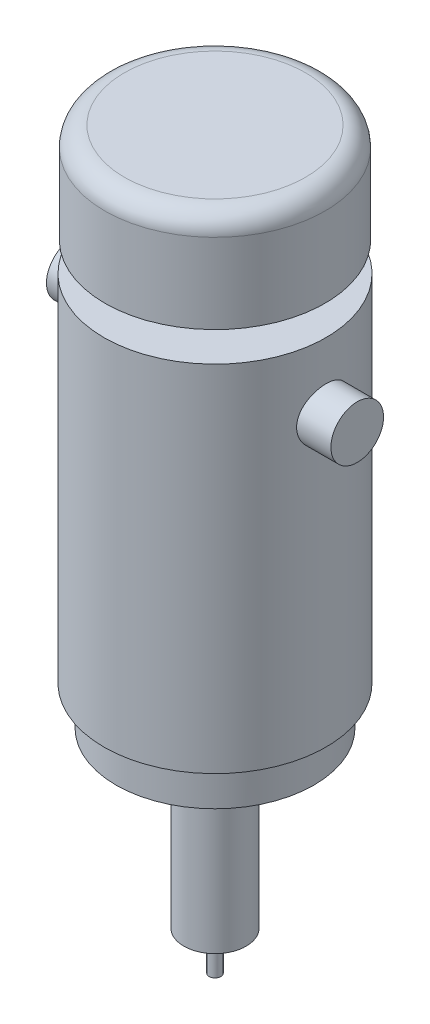
SolidWorks part; units mm, degrees
ref_plane "Front Plane" through (0, 0, 0) normal (0, 0, 1) x (1, 0, 0)
ref_plane "Top Plane" through (0, 0, 0) normal (0, 1, 0) x (1, 0, 0)
ref_plane "Right Plane" through (0, 0, 0) normal (1, 0, 0) x (0, 0, -1)
sketch "Sketch1" plane through (0, 0, 0) normal (0, 1, 0) x (1, 0, 0)
  circle A0 centre (0, 0) radius 28.5
  dimension "D1" = 57
extrude "Boss-Extrude1" add sketch "Sketch1" along normal mid plane 91
sketch "Sketch4" plane through (0, -45.5, 0) normal (0, -1, 0) x (1, 0, 0)
  circle A0 centre (0, 0) radius 25.4
  dimension "D1" = 50.8
extrude "Boss-Extrude4" add sketch "Sketch4" along normal blind 10
sketch "Sketch5" plane through (0, -55.5, 0) normal (0, -1, 0) x (1, 0, 0)
  circle A0 centre (0, 0) radius 12.65
  dimension "D1" = 25.3
extrude "Boss-Extrude5" add sketch "Sketch5" along normal blind 2.5
sketch "Sketch2" plane through (0, -58, 0) normal (0, -1, 0) x (1, 0, 0)
  circle A0 centre (0, 0) radius 8
  dimension "D1" = 16
extrude "Boss-Extrude2" add sketch "Sketch2" along normal blind 42
sketch "Sketch6" plane through (0, 45.5, 0) normal (0, 1, 0) x (1, 0, 0)
  circle A0 centre (0, 0) radius 4
  dimension "D1" = 8
extrude "Boss-Extrude6" add sketch "Sketch6" along normal blind 33
sketch "Sketch7" plane through (0, 78.5, 0) normal (0, 1, 0) x (1, 0, 0)
  circle A0 centre (0, 0) radius 28.25
  dimension "D1" = 56.5
extrude "Boss-Extrude7" add sketch "Sketch7" against normal blind 25.5
fillet "Fillet1" radius 5 1 edges at (0, 78.5, 28.25)
sketch "Sketch3" plane through (0, -100, 0) normal (0, -1, 0) x (1, 0, 0)
  circle A0 centre (0, 0) radius 1.5
  dimension "D1" = 3
extrude "Boss-Extrude3" add sketch "Sketch3" along normal blind 10
sketch "Sketch8" plane through (0, 0, 0) normal (1, 0, 0) x (0, 0, -1)
  line L0 (28.5, 45.5) -> (-28.5, 45.5) construction
  line L1 (0, 0) -> (0, 73.5) construction
  line L2 (-28.25, 73.5) -> (28.25, 73.5) construction
  circle A0 centre (0, 28.5) radius 6.75
  dimension "D1" = 13.5
  dimension "D2" = 17
extrude "Boss-Extrude8" add sketch "Sketch8" along normal mid plane 73
